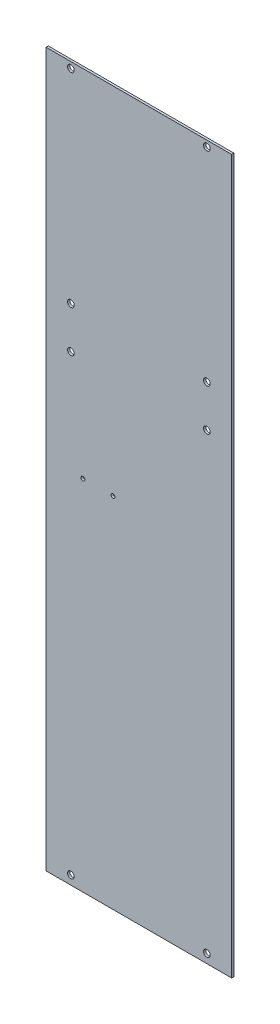
SolidWorks part; units mm, degrees
material "6061 Сплав"
ref_plane "Front Plane" through (0, 0, 0) normal (0, 0, 1) x (1, 0, 0)
ref_plane "Top Plane" through (0, 0, 0) normal (0, 1, 0) x (1, 0, 0)
ref_plane "Right Plane" through (0, 0, 0) normal (1, 0, 0) x (0, 0, -1)
sketch "Sketch1" plane through (0, 0, 0) normal (0, 0, 1) x (1, 0, 0)
  line L1 (41.6, -160) -> (-41.6, -160)
  line L2 (41.6, -160) -> (41.6, 160)
  line L3 (41.6, 160) -> (-41.6, 160)
  line L4 (-41.6, -160) -> (-41.6, 160)
  line L5 (41.6, -160) -> (-41.6, 160) construction
  line L6 (41.6, 160) -> (-41.6, -160) construction
  point P0 (0, 0)
  dimension "D1" = 83.2
  dimension "D2" = 320
extrude "Boss-Extrude1" add sketch "Sketch1" along normal blind 1
hole_wizard "Ø3.0 (3) Diameter Hole1" positions "Sketch3" profile "Sketch2" hole size "Ø3.0" standard "ANSI Metric"
sketch "Sketch3" plane through (0, 0, 1) normal (0, 0, 1) x (1, 0, 0)
  line L6 (-41.6, -160) -> (41.6, -160) construction
  line L9 (41.6, 160) -> (-41.6, 160) construction
  line L10 (0, 160) -> (0, 163.7587) construction
  line L11 (0, 160) -> (0, -152.1509) construction
  point P0 (-30.5, 66)
  point P2 (30.5, 66)
  point P15 (30.5, -156)
  point P17 (-30.5, -156)
  point P54 (-30.5, 157.3)
  point P56 (30.5, 157.3)
  point P58 (-30.5, 47.3)
  point P60 (30.5, 47.3)
  dimension "D2" = 4
  dimension "D3" = 2.7
  dimension "D4" = 4
  dimension "D5" = 30.5
  dimension "D6" = 30.5
  dimension "D7" = 94
  dimension "D8" = 30.5
  dimension "D9" = 2.7
  dimension "D10" = 94
  dimension "D11" = 30.5
  dimension "D12" = 30.5
  dimension "D13" = 30.5
  dimension "D14" = 30.5
  dimension "D15" = 30.5
  dimension "D16" = 112.7
  dimension "D17" = 112.7
sketch "Sketch2" plane through (-30.5, 66, 1) normal (1, 0, 0) x (0, -1, 0)
  line L0 (0, 0) -> (0, 1)
  line L1 (0, 1) -> (1.5, 1)
  line L2 (1.5, 1) -> (1.5, 0)
  line L5 (1.5, 0) -> (0, 0)
  line L10 (0, 1) -> (-1.5, 1) construction
  line L11 (0, -6.35) -> (0, 107.95) construction
  dimension "Hole Dia." = 3
  dimension "Hole Depth" = 1
  dimension "Drill Angle" = 180
hole_wizard "Ø1.75 (1.75) Diameter Hole1" positions "Sketch6" profile "Sketch5" hole size "Ø1.75" standard "ANSI Metric" end condition through all
sketch "Sketch6" plane through (0, 0, 1) normal (0, 0, 1) x (1, 0, 0)
  point P0 (-25.1, 0.65)
  point P3 (-11.6, 0.65)
sketch "Sketch5" plane through (-25.1, 0.65, 1) normal (1, 0, 0) x (0, -1, 0)
  line L0 (0, 0) -> (0, 1)
  line L1 (0, 1) -> (0.875, 1)
  line L2 (0.875, 1) -> (0.875, 0)
  line L5 (0.875, 0) -> (0, 0)
  line L11 (0, -6.35) -> (0, 107.95) construction
  dimension "Thru Hole Dia." = 1.75
  dimension "Thru Hole Depth" = 1
